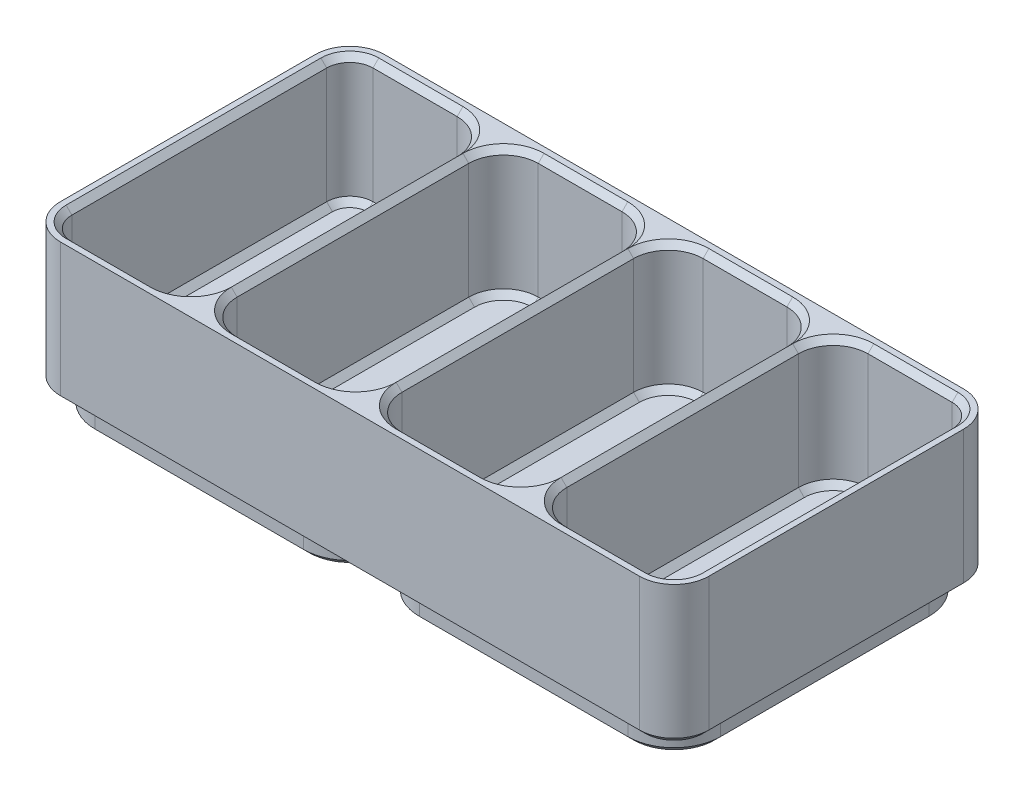
SolidWorks part; units mm, degrees
ref_plane "Front Plane" through (0, 0, 0) normal (0, 0, 1) x (1, 0, 0)
ref_plane "Top Plane" through (0, 0, 0) normal (0, 1, 0) x (1, 0, 0)
ref_plane "Right Plane" through (0, 0, 0) normal (1, 0, 0) x (0, 0, -1)
sketch "Sketch5" plane through (0, 0, 0) normal (0, 1, 0) x (1, 0, 0)
  line L1 (-22.5, -32.5) -> (22.5, -32.5)
  line L2 (-32.5, -22.5) -> (-32.5, 22.5)
  line L3 (-22.5, 32.5) -> (22.5, 32.5)
  line L4 (32.5, -22.5) -> (32.5, 22.5)
  line L5 (-32.5, -32.5) -> (32.5, 32.5) construction
  line L6 (-32.5, 32.5) -> (32.5, -32.5) construction
  arc A0 (-22.5, -32.5) -> (-32.5, -22.5) centre (-22.5, -22.5) cw
  arc A1 (22.5, -32.5) -> (32.5, -22.5) centre (22.5, -22.5) ccw
  arc A2 (22.5, 32.5) -> (32.5, 22.5) centre (22.5, 22.5) cw
  arc A3 (-32.5, 22.5) -> (-22.5, 32.5) centre (-22.5, 22.5) cw
  point P0 (0, 0)
  dimension "D3" = 10
  dimension "D1" = 65
  dimension "D2" = 65
extrude "Boss-Extrude4" add sketch "Sketch5" along normal blind 5
sketch "Sketch6" plane through (0, 5, 0) normal (0, 1, 0) x (1, 0, 0)
  line L1 (35, 35) -> (-35, 35)
  line L2 (35, 35) -> (35, -35)
  line L3 (35, -35) -> (-35, -35)
  line L4 (-35, 35) -> (-35, -35)
  line L5 (35, 35) -> (-35, -35) construction
  line L6 (35, -35) -> (-35, 35) construction
  point P0 (0, 0)
extrude "Boss-Extrude5" add sketch "Sketch6" along normal blind 30
sketch "Sketch8" plane through (0, 0, 0) normal (0, -1, 0) x (1, 0, 0)
  line L0 (-29.5711, 29.5711) -> (-22.5, 22.5)
  arc A0 (-22.5, 32.5) -> (-32.5, 22.5) centre (-22.5, 22.5) ccw construction
  circle A1 centre (-26.0355, 26.0355) radius 3
  circle A2 centre (26.0365, 26.0365) radius 3
  circle A3 centre (26.0375, -26.0355) radius 3
  circle A4 centre (-26.0345, -26.0365) radius 3
  point P8 (0, 0)
  point P15 (0.001, 0.001)
  point P18 (0.002, 0)
  point P21 (0.001, -0.001)
  point P22 (0.001, 0)
  dimension "D1" = 4
extrude "Cut-Extrude1" cut sketch "Sketch8" against normal blind 2 contours A3 | A2 | L0 A1 | L0 A1 | A4
mirror "Mirror1" about plane through (-35, 35, -35) normal (1, 0, 0) of bodies 112
fillet "Fillet1" radius 7.5 4 edges at (35, 20, -35) (35, 20, 35) (-105, 20, 35) (-105, 20, -35)
sketch "Sketch13" plane through (0, 35, 0) normal (0, 1, 0) x (1, 0, 0)
  line L0 (-36.25, -32.5) -> (-33.75, -32.5)
  line L4 (-71.8363, 32.5) -> (-71.8363, -32.5)
  line L6 (-69.3363, 32.5) -> (-69.3363, -32.5)
  line L7 (-69.3363, -32.5) -> (-71.8363, -32.5)
  line L8 (-0.6637, 32.5) -> (-0.6637, -32.5)
  line L11 (1.8363, 32.5) -> (1.8363, -32.5)
  line L12 (-0.6637, -32.5) -> (1.8363, -32.5)
  line L15 (-36.25, 32.5) -> (-36.25, -32.5)
  line L17 (-33.75, -32.5) -> (-33.75, 32.5)
  line L18 (-0.6637, -32.5) -> (1.8363, -32.5)
  line L19 (1.8363, 32.5) -> (-0.6637, 32.5)
  line L20 (-36.25, 32.5) -> (-33.75, 32.5)
  line L21 (-71.8363, 32.5) -> (-69.3363, 32.5)
  line L23 (32.5, -27.5) -> (32.5, 27.5)
  line L24 (-97.5, -32.5) -> (27.5, -32.5)
  line L25 (-102.5, 27.5) -> (-102.5, -27.5)
  line L26 (27.5, 32.5) -> (-97.5, 32.5)
  line L27 (32.5, -27.5) -> (32.5, 27.5)
  line L28 (-97.5, -32.5) -> (27.5, -32.5)
  line L29 (-102.5, 27.5) -> (-102.5, -27.5)
  line L30 (27.5, 32.5) -> (-97.5, 32.5)
  arc A21 (32.5, 27.5) -> (27.5, 32.5) centre (27.5, 27.5) ccw
  arc A22 (27.5, -32.5) -> (32.5, -27.5) centre (27.5, -27.5) ccw
  arc A23 (-102.5, -27.5) -> (-97.5, -32.5) centre (-97.5, -27.5) ccw
  arc A24 (-97.5, 32.5) -> (-102.5, 27.5) centre (-97.5, 27.5) ccw
  arc A25 (32.5, 27.5) -> (27.5, 32.5) centre (27.5, 27.5) ccw
  arc A26 (27.5, -32.5) -> (32.5, -27.5) centre (27.5, -27.5) ccw
  arc A27 (-102.5, -27.5) -> (-97.5, -32.5) centre (-97.5, -27.5) ccw
  arc A28 (-97.5, 32.5) -> (-102.5, 27.5) centre (-97.5, 27.5) ccw
  dimension "D1" = 2.5
extrude "Cut-Extrude2" cut sketch "Sketch13" against normal blind 27.5 contours L30 A28 L29 A27 L28 L4 | L15 L30 L6 L28 | L8 L30 L17 L28 | L28 A26 L27 A25 L30 L11
fillet "Fillet2" radius 7.5 12 edges at (-71.8363, 21.25, 32.5) (-36.25, 21.25, 32.5) (-0.6637, 21.25, 32.5) (-69.3363, 21.25, 32.5) (-33.75, 21.25, 32.5) (1.8363, 21.25, 32.5) (1.8363, 21.25, -32.5) (-33.75, 21.25, -32.5) (-69.3363, 21.25, -32.5) (-0.6637, 21.25, -32.5) (-36.25, 21.25, -32.5) (-71.8363, 21.25, -32.5)
chamfer "Chamfer1" distance 1.25 angle 45 64 edges at (-88.4181, 7.5, 32.5) (-74.033, 7.5, 30.3033) (-101.0355, 7.5, 31.0355) (-71.8363, 7.5, 0) (-102.5, 7.5, 0) (-74.033, 7.5, -30.3033) (-101.0355, 7.5, -31.0355) (-88.4181, 7.5, -32.5) (-52.7931, 7.5, 32.5) (-38.4467, 7.5, 30.3033) (-67.1396, 7.5, 30.3033) (-36.25, 7.5, 0) (-69.3363, 7.5, 0) (-38.4467, 7.5, -30.3033) (-67.1396, 7.5, -30.3033) (-52.7931, 7.5, -32.5) (18.4181, 7.5, 32.5) (31.0355, 7.5, 31.0355) (4.033, 7.5, 30.3033) (32.5, 7.5, 0) (1.8363, 7.5, 0) (31.0355, 7.5, -31.0355) (4.033, 7.5, -30.3033) (18.4181, 7.5, -32.5) (-17.2069, 7.5, 32.5) (-2.8604, 7.5, 30.3033) (-31.5533, 7.5, 30.3033) (-0.6637, 7.5, 0) (-33.75, 7.5, 0) (-2.8604, 7.5, -30.3033) (-31.5533, 7.5, -30.3033) (-17.2069, 7.5, -32.5) (18.4181, 35, 32.5) (31.0355, 35, 31.0355) (4.033, 35, 30.3033) (32.5, 35, 0) (1.8363, 35, 0) (31.0355, 35, -31.0355) (4.033, 35, -30.3033) (18.4181, 35, -32.5) (-17.2069, 35, 32.5) (-2.8604, 35, 30.3033) (-31.5533, 35, 30.3033) (-0.6637, 35, 0) (-33.75, 35, 0) (-2.8604, 35, -30.3033) (-31.5533, 35, -30.3033) (-17.2069, 35, -32.5) (-52.7931, 35, 32.5) (-38.4467, 35, 30.3033) (-67.1396, 35, 30.3033) (-36.25, 35, 0) (-69.3363, 35, 0) (-38.4467, 35, -30.3033) (-67.1396, 35, -30.3033) (-52.7931, 35, -32.5) (-88.4181, 35, 32.5) (-74.033, 35, 30.3033) (-101.0355, 35, 31.0355) (-71.8363, 35, 0) (-102.5, 35, 0) (-74.033, 35, -30.3033) (-101.0355, 35, -31.0355) (-88.4181, 35, -32.5)
chamfer "Chamfer2" distance 1.25 angle 45 24 edges at (-70, 0, -32.5) (-40.4289, 0, -29.5711) (-99.5711, 0, -29.5711) (-37.5, 0, 0) (-102.5, 0, 0) (-40.4289, 0, 29.5711) (-99.5711, 0, 29.5711) (-70, 0, 32.5) (-35, 5, -35) (-102.8033, 5, -32.8033) (32.8033, 5, -32.8033) (-105, 5, 0) (35, 5, 0) (-102.8033, 5, 32.8033) (32.8033, 5, 32.8033) (-35, 5, 35) (0, 0, -32.5) (-29.5711, 0, -29.5711) (29.5711, 0, -29.5711) (-32.5, 0, 0) (32.5, 0, 0) (-29.5711, 0, 29.5711) (29.5711, 0, 29.5711) (0, 0, 32.5)
